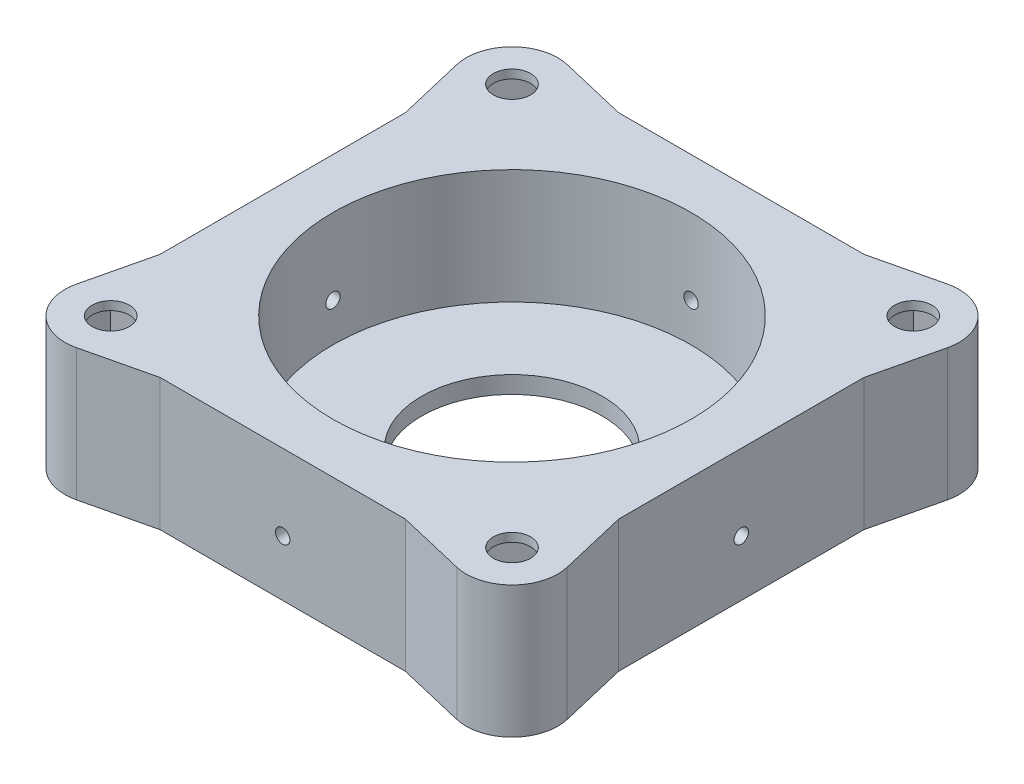
SolidWorks part; units mm, degrees
ref_plane "Front Plane" through (0, 0, 0) normal (0, 0, 1) x (1, 0, 0)
ref_plane "Top Plane" through (0, 0, 0) normal (0, 1, 0) x (1, 0, 0)
ref_plane "Right Plane" through (0, 0, 0) normal (1, 0, 0) x (0, 0, -1)
sketch "Sketch1" plane through (0, 0, 0) normal (0, 1, 0) x (1, 0, 0)
  line L0 (0, 35) -> (0, -35) construction
  line L1 (35, -35) -> (-35, -35)
  line L2 (35, -35) -> (35, 35)
  line L3 (35, 35) -> (-35, 35)
  line L4 (-35, -35) -> (-35, 35)
  line L5 (35, -35) -> (-35, 35) construction
  line L6 (35, 35) -> (-35, -35) construction
  line L7 (-35, 0) -> (35, 0) construction
  line L8 (-33.1578, 42.785) -> (7.8292, 33.0863)
  line L9 (-42.785, 33.1578) -> (-33.0863, -7.8292)
  line L10 (42.785, 33.1578) -> (33.0863, -7.8292)
  line L11 (33.1578, 42.785) -> (-7.8292, 33.0863)
  line L12 (-42.785, -33.1578) -> (-33.0863, 7.8292)
  line L13 (-33.1578, -42.785) -> (7.8292, -33.0863)
  line L14 (33.1578, -42.785) -> (-7.8292, -33.0863)
  line L15 (42.785, -33.1578) -> (33.0863, 7.8292)
  line L17 (40, -40) -> (-40, -40)
  line L18 (40, -40) -> (40, 40)
  line L19 (40, 40) -> (-40, 40)
  line L20 (-40, -40) -> (-40, 40)
  line L21 (40, -40) -> (-40, 40) construction
  line L22 (40, 40) -> (-40, -40) construction
  circle A0 centre (0, 0) radius 15.75
  circle A1 centre (0, 0) radius 34
  circle A2 centre (-35, 35) radius 3.25
  circle A3 centre (0, 0) radius 40
  circle A4 centre (-35, 35) radius 8
  circle A5 centre (35, 35) radius 3.25
  circle A6 centre (35, 35) radius 8
  circle A7 centre (-35, -35) radius 3.25
  circle A8 centre (-35, -35) radius 8
  circle A9 centre (35, -35) radius 3.25
  circle A10 centre (35, -35) radius 8
  dimension "D1" = 31.5
  dimension "D2" = 68
  dimension "D3" = 6.5
  dimension "D5" = 80
  dimension "D4" = 16
  dimension "D6" = 70
extrude "Boss-Extrude1" add sketch "Sketch1" along normal blind 19.5 contours L19 A4 L20 | L3 A4 L19 L20 L4 A2 | L4 A4 L3 A2 | A4 L9 L20 | A4 L20 L9 A3 L4 | A3 L9 L20 | L4 A3 L9 | L9 A3 L12 L4 | A3 L20 L12 | L12 A3 L4 | L20 A8 L4 A3 L12 | L12 A8 L20 | A8 L17 L20 | A8 L20 L17 L1 A7 L4 | A8 L4 A7 L1 | L4 A8 L1 A3 | L4 A3 L1 L13 L14 A1 L9 L12 | L3 A3 L4 L9 L12 A1 L11 L8 | A1 L12 L9 | A4 L4 A3 L3 | A4 L3 A3 L8 L19 | A4 L19 L8 | A3 L19 L8 | L8 A3 L3 | L11 A3 L8 L3 | A1 L8 L11 | L3 A3 L11 | L2 A3 L3 L11 L8 A1 L15 L10 | L3 A6 L19 L11 A3 | A3 L11 L19 | L19 A6 L11 | L2 A6 L3 A3 | A6 L2 A5 L3 | A6 L3 A5 L2 L18 L19 | A6 L19 L18 | L10 A6 L18 | L18 A6 L2 A3 L10 | A3 L18 L10 | L10 A3 L2 | L15 A3 L10 L2 | A3 L15 L18 | L2 A3 L15 | A1 L10 L15 | L1 A3 L2 L15 L10 A1 L13 L14 | A10 L18 L15 A3 L2 | A10 L15 L18 | A10 L2 A3 L1 | L18 A10 L2 A9 L1 L17 | L2 A10 L1 A9 | A10 L18 L17 | A10 L17 L14 | A10 L1 A3 L14 L17 | L14 A3 L1 | A3 L17 L14 | A3 L14 L1 L13 | A1 L14 L13 | L1 A3 L13 | A3 L13 L17 | L1 A8 L17 L13 A3 | L17 A8 L13 | A1 A0 region at (-27.625, 0, 37.5886) region at (-28.9419, 0, 28.9419) region at (-31.2062, 0, 31.2062) region at (-21.8672, 0, 37.555) region at (-24.6184, 0, 24.6184) region at (-10.9152, 0, 35.995) region at (-37.555, 0, 21.8672) region at (-30.8311, 0, 41.5907) region at (-27.2274, 0, 40.8217) region at (0, 0, 37.8149) region at (-35.995, 0, 10.9152) region at (-12.614, 0, 39.3478) region at (-40.8217, 0, 27.2274) region at (24.6184, 0, 24.6184) region at (10.9152, 0, 35.995) region at (0, 0, 34.191) region at (-37.8149, 0, 0) region at (-39.3478, 0, 12.614) region at (12.614, 0, 39.3478) region at (28.9419, 0, 28.9419) region at (21.8672, 0, 37.555) region at (0, 0, 33.0383) region at (-35.995, 0, -10.9152) region at (-24.6184, 0, -24.6184) region at (-34.191, 0, 0) region at (-39.3478, 0, -12.614) region at (27.2274, 0, 40.8217) region at (31.2062, 0, 31.2062) region at (29.375, 0, 35.1838) region at (37.555, 0, 21.8672) region at (35.995, 0, 10.9152) region at (34.191, 0, 0) region at (-37.555, 0, -21.8672) region at (-28.9419, 0, -28.9419) region at (-40.8217, 0, -27.2274) region at (30.8311, 0, 41.5907) region at (37.8149, 0, 0) region at (39.3478, 0, 12.614) region at (24.6184, 0, -24.6184) region at (-37.5886, 0, -27.625) region at (-31.2062, 0, -31.2062) region at (-10.9152, 0, -35.995) region at (-21.8672, 0, -37.555) region at (0, 0, -34.191) region at (-40.5144, 0, -40.5144) region at (40.8217, 0, 27.2274) region at (35.995, 0, -10.9152) region at (39.3478, 0, -12.614) region at (0, 0, -37.8149) region at (-12.614, 0, -39.3478) region at (-27.2274, 0, -40.8217) region at (28.9419, 0, -28.9419) region at (37.555, 0, -21.8672) region at (40.8217, 0, -27.2274) region at (10.9152, 0, -35.995) region at (12.614, 0, -39.3478) region at (31.2062, 0, -31.2062) region at (35.1838, 0, -29.375) region at (21.8672, 0, -37.555) region at (41.5907, 0, -30.8311)
sketch "Sketch2" plane through (0, 19.5, 0) normal (0, 1, 0) x (1, 0, 0)
  circle A0 centre (0, 0) radius 31.25
  dimension "D1" = 62.5
extrude "Cut-Extrude1" cut sketch "Sketch2" against normal blind 16.5
sketch "Sketch3" plane through (0, 0, 0) normal (0, -1, 0) x (1, 0, 0)
  circle A0 centre (-35, 35) radius 5.25
  circle A1 centre (35, 35) radius 5.25
  circle A2 centre (35, -35) radius 5.25
  circle A3 centre (-35, -35) radius 5.25
  dimension "D1" = 10.5
extrude "Cut-Extrude2" cut sketch "Sketch3" against normal blind 10
sketch "Sketch4" plane through (0, 0, 40) normal (0, 0, 1) x (1, 0, 0)
  line L0 (0, 0) -> (0, 19.5) construction
  line L1 (21.3883, 0) -> (-21.3883, 0) construction
  line L2 (21.3883, 19.5) -> (-21.3883, 19.5) construction
  circle A0 centre (0, 9.75) radius 1.25
  dimension "D1" = 2.5
extrude "Cut-Extrude3" cut sketch "Sketch4" against normal up to surface (80 mm away) up to face at (0, 9.75, -40)
sketch "Sketch5" plane through (40, 0, 0) normal (1, 0, 0) x (0, 0, -1)
  line L0 (0, 0) -> (0, 19.5) construction
  line L1 (-21.3883, 19.5) -> (21.3883, 19.5) construction
  circle A0 centre (0, 9.75) radius 1.25
  dimension "D1" = 2.5
extrude "Cut-Extrude4" cut sketch "Sketch5" against normal up to surface (80 mm away) up to face at (-40, 9.75, 0)
sketch "Sketch6" plane through (0, 19.5, 0) normal (0, 1, 0) x (1, 0, 0)
  line L12 (21.3883, -40) -> (33.1578, -42.785)
  line L13 (42.785, -33.1578) -> (40, -21.3883)
  line L14 (40, -21.3883) -> (40, 21.3883)
  line L15 (40, 21.3883) -> (42.785, 33.1578)
  line L16 (33.1578, 42.785) -> (21.3883, 40)
  line L17 (21.3883, 40) -> (-21.3883, 40)
  line L18 (-21.3883, 40) -> (-33.1578, 42.785)
  line L19 (-42.785, 33.1578) -> (-40, 21.3883)
  line L20 (-40, 21.3883) -> (-40, -21.3883)
  line L21 (-40, -21.3883) -> (-42.785, -33.1578)
  line L22 (-33.1578, -42.785) -> (-21.3883, -40)
  line L23 (-21.3883, -40) -> (21.3883, -40)
  line L24 (21.3883, -40) -> (33.1578, -42.785)
  line L25 (42.785, -33.1578) -> (40, -21.3883)
  line L26 (40, -21.3883) -> (40, 21.3883)
  line L27 (40, 21.3883) -> (42.785, 33.1578)
  line L28 (33.1578, 42.785) -> (21.3883, 40)
  line L29 (21.3883, 40) -> (-21.3883, 40)
  line L30 (-21.3883, 40) -> (-33.1578, 42.785)
  line L31 (-42.785, 33.1578) -> (-40, 21.3883)
  line L32 (-40, 21.3883) -> (-40, -21.3883)
  line L33 (-40, -21.3883) -> (-42.785, -33.1578)
  line L34 (-33.1578, -42.785) -> (-21.3883, -40)
  line L35 (-21.3883, -40) -> (21.3883, -40)
  circle A0 centre (0, 0) radius 31.25 construction
  circle A1 centre (35, 35) radius 3.25 construction
  circle A2 centre (-35, 35) radius 3.25 construction
  circle A3 centre (35, -35) radius 3.25 construction
  arc A4 (33.1578, -42.785) -> (42.785, -33.1578) centre (35, -35) ccw
  arc A5 (42.785, 33.1578) -> (33.1578, 42.785) centre (35, 35) ccw
  arc A6 (-33.1578, 42.785) -> (-42.785, 33.1578) centre (-35, 35) ccw
  arc A7 (-42.785, -33.1578) -> (-33.1578, -42.785) centre (-35, -35) ccw
  arc A8 (33.1578, -42.785) -> (42.785, -33.1578) centre (35, -35) ccw
  arc A9 (42.785, 33.1578) -> (33.1578, 42.785) centre (35, 35) ccw
  arc A10 (-33.1578, 42.785) -> (-42.785, 33.1578) centre (-35, 35) ccw
  arc A11 (-42.785, -33.1578) -> (-33.1578, -42.785) centre (-35, -35) ccw
  circle A12 centre (-35, -35) radius 3.25 construction
  circle A13 centre (0, 0) radius 31.25
  circle A14 centre (35, 35) radius 3.25
  circle A15 centre (-35, 35) radius 3.25
  circle A16 centre (35, -35) radius 3.25
  circle A17 centre (-35, -35) radius 3.25
  dimension "D1" = 0
extrude "Boss-Extrude4" add sketch "Sketch6" along normal blind 3.5
sketch "Sketch7" plane through (0, 0, 0) normal (0, -1, 0) x (1, 0, 0)
  line L0 (-35, 35) -> (-38.7123, 38.7123) construction
  line L1 (-29.1444, 33.431) -> (-30.7134, 39.2866)
  line L2 (-30.7134, 39.2866) -> (-36.569, 40.8556)
  line L3 (-36.569, 40.8556) -> (-40.8556, 36.569)
  line L4 (-40.8556, 36.569) -> (-39.2866, 30.7134)
  line L5 (-39.2866, 30.7134) -> (-33.431, 29.1444)
  line L6 (-33.431, 29.1444) -> (-29.1444, 33.431)
  line L7 (39.2866, 30.7134) -> (40.8556, 36.569)
  line L8 (40.8556, 36.569) -> (36.569, 40.8556)
  line L9 (36.569, 40.8556) -> (30.7134, 39.2866)
  line L10 (30.7134, 39.2866) -> (29.1444, 33.431)
  line L11 (29.1444, 33.431) -> (33.431, 29.1444)
  line L12 (33.431, 29.1444) -> (39.2866, 30.7134)
  line L13 (30.7134, -39.2866) -> (36.569, -40.8556)
  line L14 (36.569, -40.8556) -> (40.8556, -36.569)
  line L15 (40.8556, -36.569) -> (39.2866, -30.7134)
  line L16 (39.2866, -30.7134) -> (33.431, -29.1444)
  line L17 (33.431, -29.1444) -> (29.1444, -33.431)
  line L18 (29.1444, -33.431) -> (30.7134, -39.2866)
  line L19 (-39.2866, -30.7134) -> (-40.8556, -36.569)
  line L20 (-40.8556, -36.569) -> (-36.569, -40.8556)
  line L21 (-36.569, -40.8556) -> (-30.7134, -39.2866)
  line L22 (-30.7134, -39.2866) -> (-29.1444, -33.431)
  line L23 (-29.1444, -33.431) -> (-33.431, -29.1444)
  line L24 (-33.431, -29.1444) -> (-39.2866, -30.7134)
  line L25 (0, 40) -> (0, -40) construction
  line L26 (21.3883, 40) -> (-21.3883, 40) construction
  line L27 (21.3883, -40) -> (-21.3883, -40) construction
  circle A0 centre (-35, 35) radius 5.25 construction
  point P32 (0, 0)
  dimension "D1" = 10.5
  dimension "D2" = 4
extrude "Cut-Extrude5" cut sketch "Sketch7" against normal offset from surface (21.5 mm away) 1.5 up to face at (35, 23, 38.25)
